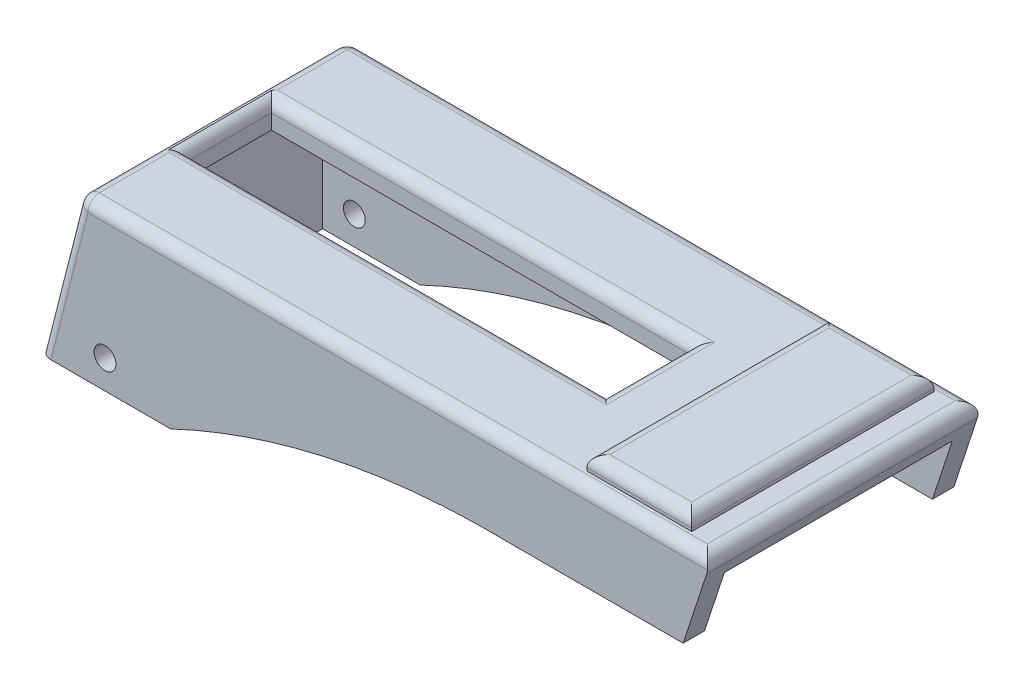
SolidWorks part; units mm, degrees
ref_plane "Front Plane" through (0, 0, 0) normal (0, 0, 1) x (1, 0, 0)
ref_plane "Top Plane" through (0, 0, 0) normal (0, 1, 0) x (1, 0, 0)
ref_plane "Right Plane" through (0, 0, 0) normal (1, 0, 0) x (0, 0, -1)
sketch "Sketch5" plane through (0, 0, 0) normal (0, 0, 1) x (1, 0, 0)
  line L0 (-26.924, 7.0167) -> (-30.48, -7.0168)
  line L1 (-26.924, -7.0168) -> (26.924, -7.0168)
  line L2 (-26.924, -7.0168) -> (-26.924, 7.0167)
  line L3 (-26.924, 7.0167) -> (26.924, 7.0167)
  line L4 (26.924, -7.0168) -> (26.924, 7.0167)
  line L5 (-26.924, -7.0168) -> (26.924, 7.0167) construction
  line L6 (-26.924, 7.0167) -> (26.924, -7.0168) construction
  line L7 (-30.48, -7.0168) -> (-26.924, -7.0168)
  line L8 (-26.924, -7.0168) -> (-26.924, 7.0167)
  line L9 (26.924, 7.0167) -> (29.464, 7.0167)
  line L10 (29.464, 7.0167) -> (26.924, -0.7176)
  line L11 (26.924, -0.7176) -> (26.924, 7.0167)
  line L13 (26.416, 7.0167) -> (17.0688, 7.0167)
  line L14 (26.416, 7.0167) -> (26.416, 8.2867)
  line L15 (26.416, 8.2867) -> (17.0688, 8.2867)
  line L16 (17.0688, 7.0167) -> (17.0688, 8.2867)
  point P0 (0, 0)
  point P13 (26.416, 7.6517)
  dimension "D1" = 53.848
  dimension "D2" = 14.0335
  dimension "D3" = 3.556
  dimension "D4" = 2.54
  dimension "D5" = 7.7343
  dimension "D6" = 9.3472
  dimension "D7" = 1.27
  dimension "D8" = 0.508
extrude "Boss-Extrude2" add sketch "Sketch5" along normal blind 24.13 contours L1 L4 L3 L2 | L10 L9 L4 | L0 L7 L2 | L14 L13 L16 L15 region at (-28.1093, -2.3389, 0) region at (0, 0, 0) region at (27.7707, 4.4386, 0)
sketch "Sketch7" plane through (0, 0, 24.13) normal (0, 0, 1) x (1, 0, 0)
  line L0 (-30.48, -7.0168) -> (26.924, -7.0168) construction
  line L2 (26.924, -0.7176) -> (-18.7706, -0.7176)
  line L3 (26.924, -0.7176) -> (26.924, -7.0168)
  line L4 (26.924, -7.0168) -> (-18.7706, -7.0168)
  line L5 (-18.7706, -0.7176) -> (-18.7706, -7.0168)
  line L6 (8.8626, -0.7176) -> (-18.7706, -0.7176)
  line L7 (-18.7706, -0.7176) -> (-18.7706, -7.0168)
  circle A0 centre (-24.6126, -4.4768) radius 0.9716
  spline S0 degree 2 poles (-18.7706, -7.0168) (-5.7784, -0.8913) (8.8626, -0.7176) knots 0 0 0 1 1 1
  line M5 (-30.48, -7.0168) -> (26.924, -7.0168)
  line M6 (26.924, -7.0168) -> (26.924, -0.7176)
  dimension "D1" = 1.9431
  dimension "D2" = 5.8674
  dimension "D3" = 2.54
  dimension "D4" = 5.842
extrude "Cut-Extrude3" cut sketch "Sketch7" against normal through all contours S0 L2 M5 M6 | A0 region at (8.0725, -4.1891, 24.13)
sketch "Sketch8" plane through (0, 8.2867, 0) normal (0, 1, 0) x (1, 0, 0)
  line L0 (-55, 0) -> (55, 0) construction
  line L1 (26.416, 0) -> (17.0688, 0)
  line L2 (26.416, 0) -> (26.416, -1.27)
  line L3 (26.416, -1.27) -> (17.0688, -1.27)
  line L4 (17.0688, 0) -> (17.0688, -1.27)
  line L5 (26.416, -24.13) -> (26.416, 0) construction
  line L6 (17.0688, -24.13) -> (17.0688, 0) construction
  line L7 (17.0688, -24.13) -> (17.0688, 0) construction
  line L8 (26.416, -24.13) -> (17.0688, -24.13)
  line L9 (26.416, -24.13) -> (26.416, -22.86)
  line L10 (26.416, -22.86) -> (17.0688, -22.86)
  line L11 (17.0688, -24.13) -> (17.0688, -22.86)
  dimension "D1" = 1.27
  dimension "D2" = 1.27
extrude "Cut-Extrude4" cut sketch "Sketch8" against normal up to surface (1.27 mm away) up to face at (27.94, 7.0167, 12.065)
sketch "Sketch9" plane through (0, 7.0167, 0) normal (0, 1, 0) x (1, 0, 0)
  line L0 (29.464, -12.065) -> (-30.48, -12.065) construction
  line L1 (29.464, -24.13) -> (29.464, 0) construction
  line L2 (-30.48, -24.13) -> (-30.48, 0) construction
  line L3 (-26.924, -24.13) -> (-26.924, 0) construction
  line L4 (-25.654, -15.875) -> (11.811, -15.875)
  line L5 (-25.654, -15.875) -> (-25.654, -8.255)
  line L6 (-25.654, -8.255) -> (11.811, -8.255)
  line L7 (11.811, -15.875) -> (11.811, -8.255)
  line L8 (-25.654, -15.875) -> (11.811, -8.255) construction
  line L9 (-25.654, -8.255) -> (11.811, -15.875) construction
  point P6 (-6.9215, -12.065)
  point P11 (-4.0361, -12.065)
  dimension "D1" = 7.62
  dimension "D2" = 1.27
  dimension "D3" = 37.465
extrude "Cut-Extrude5" cut sketch "Sketch9" against normal through all
sketch "Sketch10" plane through (0, -7.0168, 0) normal (0, -1, 0) x (1, 0, 0)
  line L0 (0, -8.4169) -> (0, 8.4169) construction
  line L5 (29.464, 24.13) -> (29.464, 0) construction
  line L6 (29.464, 22.225) -> (-27.432, 22.225)
  line L9 (29.464, 22.225) -> (29.464, 1.905)
  line L10 (29.464, 1.905) -> (-27.432, 1.905)
  line L11 (-27.432, 22.225) -> (-27.432, 1.905)
  line L12 (-30.48, 24.13) -> (-30.48, 0) construction
  line L14 (8.8626, 24.13) -> (-18.7706, 24.13) construction
  line L15 (8.4169, 0) -> (-8.4169, 0) construction
  point P0 (0, 11.8139)
  point P11 (29.464, 21.5155)
  dimension "D1" = 3.048
  dimension "D2" = 1.905
  dimension "D3" = 1.905
extrude "Cut-Extrude6" cut sketch "Sketch10" against normal blind 11.684
fillet "Fillet1" radius 1.016 10 edges at (1.27, 7.0167, 0) (-26.924, 7.0167, 12.065) (1.27, 7.0167, 24.13) (-25.654, 7.0167, 12.065) (-6.9215, 7.0167, 15.875) (11.811, 7.0167, 12.065) (-6.9215, 7.0167, 8.255) (29.464, 7.0167, 12.065) (-28.702, 0, 0) (-28.702, 0, 24.13)
fillet "Fillet5" radius 1.016 4 edges at (21.7424, 8.2867, 22.86) (17.0688, 8.2867, 12.065) (21.7424, 8.2867, 1.27) (26.416, 8.2867, 12.065)
